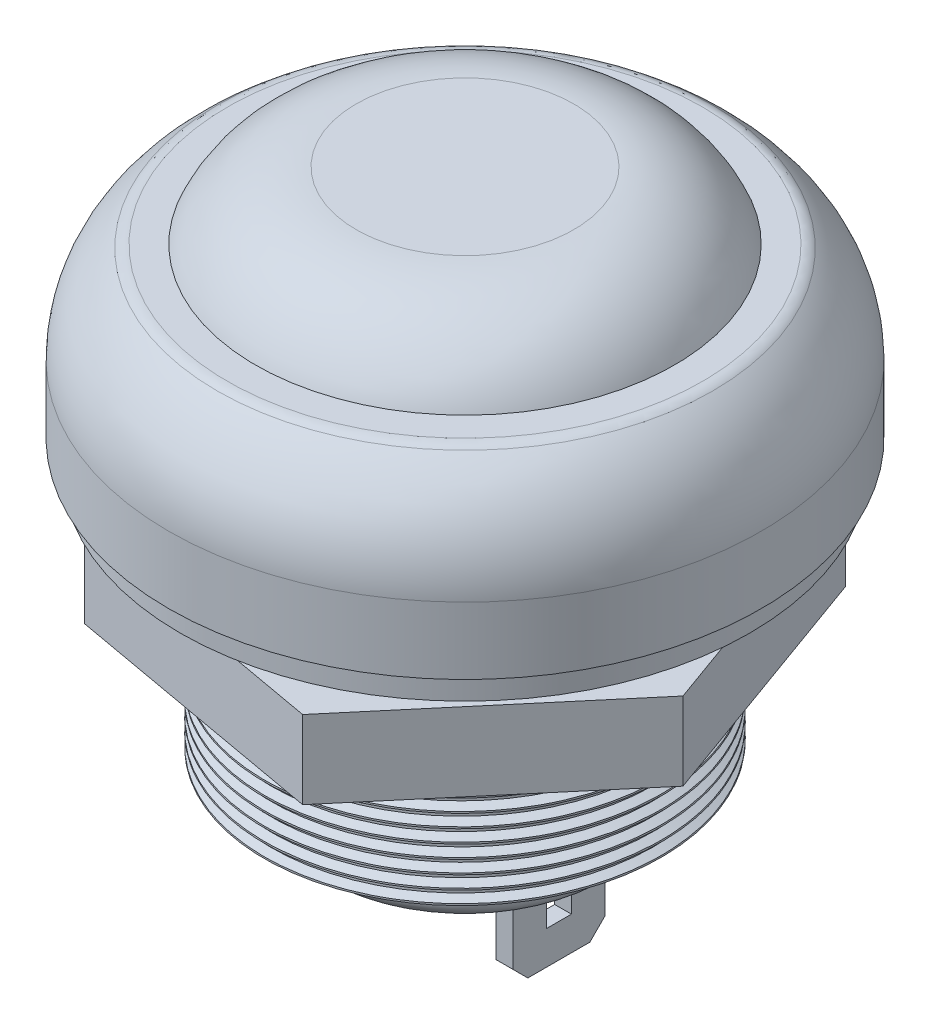
SolidWorks part; units mm, degrees
ref_plane "Front Plane" through (0, 0, 0) normal (0, 0, 1) x (1, 0, 0)
ref_plane "Top Plane" through (0, 0, 0) normal (0, 1, 0) x (1, 0, 0)
ref_plane "Right Plane" through (0, 0, 0) normal (1, 0, 0) x (0, 0, -1)
sketch "Sketch1" plane through (0, 0, 0) normal (0, 0, 1) x (1, 0, 0)
  line L0 (0, 6.5) -> (0, -6.5)
  line L1 (0, 6.5) -> (0, -6.5) construction
  line L2 (0, 6.5) -> (8.84, 6.5)
  line L3 (8.84, 6.5) -> (8.84, 1.5)
  line L4 (8.84, 1.5) -> (6.74, 1.5)
  line L5 (6.74, 1.5) -> (6.74, -0.3)
  line L6 (6.74, -0.3) -> (5.915, -0.3)
  line L7 (5.915, -0.3) -> (5.915, -6.5)
  line L8 (5.915, -6.5) -> (0, -6.5)
  dimension "D1" = 5.915
  dimension "D2" = 6.74
  dimension "D3" = 13
  dimension "D4" = 8.84
  dimension "D5" = 6.2
  dimension "D6" = 8
revolve "Revolve1" add sketch "Sketch1" angle 360 about L1
sketch "Sketch2" plane through (0, -6.5, 0) normal (0, -1, 0) x (1, 0, 0)
  circle A0 centre (0, 0) radius 4.295
  dimension "D1" = 8.59
extrude "Boss-Extrude1" add sketch "Sketch2" along normal blind 1.5 separate body
sketch "Sketch3" plane through (0, -8, 0) normal (0, -1, 0) x (1, 0, 0)
  line L0 (0, 4.295) -> (0, -4.295) construction
  line L1 (-2.55, 4.295) -> (-2.55, -4.295) construction
  line L2 (2.55, 4.295) -> (2.55, -4.295) construction
  line L3 (-4.295, 0) -> (4.295, 0) construction
  line L4 (-4.295, -1.375) -> (4.295, -1.375) construction
  line L5 (-4.295, 1.375) -> (4.295, 1.375) construction
  line L7 (2.3, -1.375) -> (2.8, -1.375)
  line L8 (2.3, -1.375) -> (2.3, 1.375)
  line L9 (2.3, 1.375) -> (2.8, 1.375)
  line L10 (2.8, -1.375) -> (2.8, 1.375)
  line L11 (2.3, -1.375) -> (2.8, 1.375) construction
  line L12 (2.3, 1.375) -> (2.8, -1.375) construction
  line L13 (-2.8, -1.375) -> (-2.3, -1.375)
  line L14 (-2.8, -1.375) -> (-2.8, 1.375)
  line L15 (-2.8, 1.375) -> (-2.3, 1.375)
  line L16 (-2.3, -1.375) -> (-2.3, 1.375)
  line L17 (-2.8, -1.375) -> (-2.3, 1.375) construction
  line L18 (-2.8, 1.375) -> (-2.3, -1.375) construction
  circle A0 centre (0, 0) radius 4.295 construction
  point P15 (2.55, 0)
  point P20 (-2.55, 0)
  dimension "D5" = 0.5
  dimension "D6" = 0.5
  dimension "D1" = 2.55
  dimension "D2" = 2.55
  dimension "D3" = 1.375
  dimension "D4" = 1.375
extrude "Boss-Extrude2" add sketch "Sketch3" along normal blind 2.6 separate body
sketch "Sketch5" plane through (0, 6.5, 0) normal (0, 1, 0) x (1, 0, 0)
  circle A0 centre (0, 0) radius 6.25
  dimension "D1" = 12.5
extrude "Boss-Extrude3" add sketch "Sketch5" along normal blind 2 separate body
sketch "Sketch6" plane through (0, 8.5, 0) normal (0, 1, 0) x (1, 0, 0)
  circle A0 centre (0, 0) radius 3.25
  dimension "D1" = 6.5
sketch "Sketch8" plane through (0, 0, 0) normal (0, 0, 1) x (1, 0, 0)
  line L1 (0, 8.5) -> (0, -8.0216) construction
  line L2 (3.25, 8.5) -> (-3.25, 8.5) construction
  line L7 (3.25, 8.5) -> (3.25, 9.8195)
  line L8 (3.25, 9.8195) -> (7.0951, 9.8195)
  line L9 (7.0951, 9.8195) -> (7.0951, 6.5)
  line L10 (7.0951, 6.5) -> (6.25, 6.5)
  arc A0 (3.25, 8.5) -> (6.25, 6.5) centre (3.25, 5.25) cw
  dimension "D7" = 3.25
  dimension "D1" = 1.3195
  dimension "D2" = 3.3195
  dimension "D3" = 3.8451
  dimension "D4" = 3.25
  dimension "D5" = 6.25
  dimension "D6" = 0.8451
revolve "Cut-Revolve1" cut sketch "Sketch8" angle 360 about L1
sketch "Sketch9" plane through (0, 0, 0) normal (0, 0, 1) x (1, 0, 0)
  line L0 (0, 8.5) -> (0, -8) construction
  line L1 (3.25, 8.5) -> (-3.25, 8.5) construction
  line L2 (-4.295, -8) -> (4.295, -8) construction
  line L3 (8.84, 3.5) -> (9.5988, 3.5)
  line L4 (9.5988, 3.5) -> (9.5988, 6.8651)
  line L5 (9.5988, 6.8651) -> (7.25, 6.8651)
  line L7 (7.25, 6.5) -> (7.25, 6.8651)
  arc A0 (7.25, 6.5) -> (8.84, 3.5) centre (5.2148, 3.5) cw
  point P6 (9.5988, 5.1826)
  dimension "D5" = 3.6252
  dimension "D1" = 7.25
  dimension "D2" = 9.5988
  dimension "D3" = 3.5
  dimension "D4" = 6.8651
  dimension "D6" = 3.3953
revolve "Cut-Revolve2" cut sketch "Sketch9" angle 360 about L0
thread "Thread1" pitch 0.3969 method cut profile "Thread Profile1" start angle 0, offset 1, length 0, pitch 0.3969, diameter 11.83
ref_plane "Plane1" through (5.915, -7.5, 0) normal (0, 0, 1) x (1, 0, 0)
sketch "Thread Profile1" plane through (5.915, -7.5, 0) normal (0, 0, 1) x (1, 0, 0)
  line L0 (0, 0) -> (0, 0.3969) construction
  line L11 (0, 0) -> (0, 0.3473)
  line L12 (0, 0.3473) -> (-0.2148, 0.2232)
  line L13 (-0.2148, 0.2232) -> (-0.2148, 0.124)
  line L15 (-0.2148, 0.124) -> (0, 0)
  line L17 (-0.2148, 0.1736) -> (0, 0.1736) construction
  point P2 (0, 0)
  dimension "Pitch" = 0.3969
  dimension "Profile_Angle" = 60
  dimension "Profile_Land" = 0.0992
  dimension "Profile_Height" = 0.2148
sketch "Sketch14" plane through (-2.8, 0, 0) normal (-1, 0, 0) x (0, 0, 1)
  line L4 (1.375, -8) -> (-1.375, -8) construction
  line L5 (0.375, -8) -> (-0.375, -8)
  line L8 (0.375, -9) -> (-0.375, -9)
  line L9 (-0.375, -9) -> (-0.375, -9.6)
  line L10 (-0.375, -9.6) -> (0.375, -9.6)
  line L11 (0.375, -9.6) -> (0.375, -9)
  line L12 (0.375, -9) -> (-0.375, -9) construction
  line L13 (-0.375, -8) -> (-0.375, -9.6)
  line L14 (-0.375, -9.6) -> (0.375, -9.6)
  line L15 (0.375, -9.6) -> (0.375, -8)
  dimension "D1" = 1
extrude "Cut-Extrude1" cut sketch "Sketch14" against normal up to surface (5.6 mm away) up to face at (2.8, -9.3, 0)
chamfer "Chamfer1" distance 0.45 angle 45 2 edges at (-2.55, -10.6, 1.375) (-2.55, -10.6, -1.375)
chamfer "Chamfer2" distance 0.45 angle 45 2 edges at (2.55, -10.6, 1.375) (2.55, -10.6, -1.375)
fillet "Fillet1" radius 0.5 1 edges at (0, 6.5, 7.25)
fillet "Fillet2" radius 0.5 1 edges at (0, -8, -4.295)
sketch "Sketch15" plane through (0, 1.5, 0) normal (0, -1, 0) x (1, 0, 0)
  circle A0 centre (0, 0) radius 8.5
  circle A1 centre (0, 0) radius 6.8
  dimension "D1" = 17
  dimension "D2" = 1.7
extrude "Boss-Extrude4" add sketch "Sketch15" along normal blind 0.8 separate body
ref_plane "Plane2" through (0, -0.5, 0) normal (0, -1, 0) x (-1, 0, 0)
sketch "Sketch16" plane through (0, -0.5, 0) normal (0, -1, 0) x (1, 0, 0)
  line L1 (5.1957, -6.1541) -> (7.9274, 1.4225)
  line L2 (7.9274, 1.4225) -> (2.7318, 7.5766)
  line L3 (2.7318, 7.5766) -> (-5.1957, 6.1541)
  line L4 (-5.1957, 6.1541) -> (-7.9274, -1.4225)
  line L5 (-7.9274, -1.4225) -> (-2.7318, -7.5766)
  line L6 (-2.7318, -7.5766) -> (5.1957, -6.1541)
  circle A0 centre (0, 0) radius 6.975 construction
  circle A1 centre (0, 0) radius 5.5
  dimension "D1" = 13.95
  dimension "D2" = 11
  dimension "D3" = 7.9274
extrude "Boss-Extrude5" add sketch "Sketch16" along normal blind 2.33 separate body
